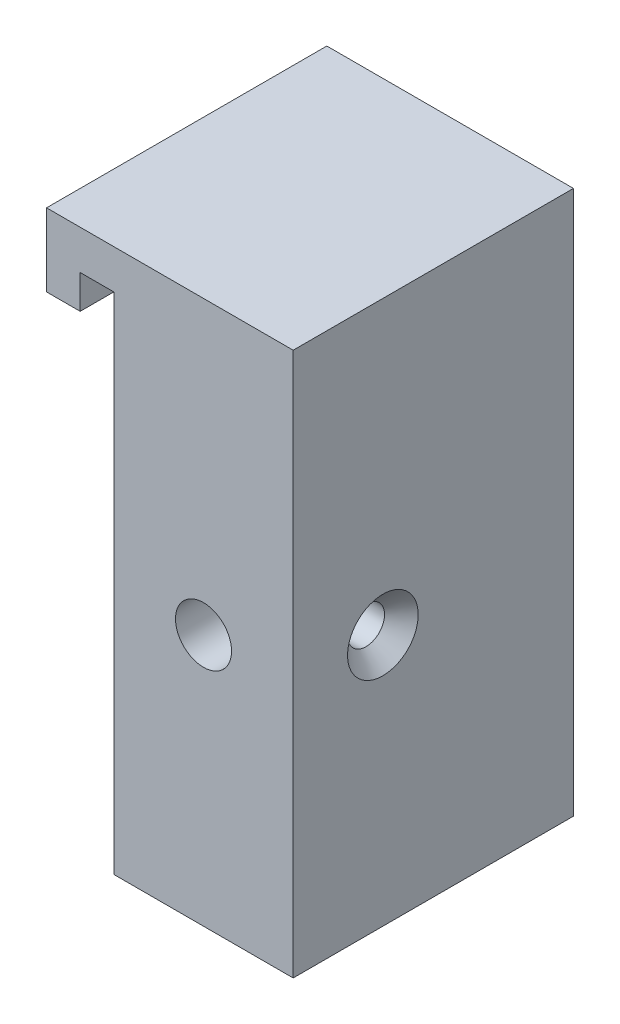
SolidWorks part; units mm, degrees
ref_plane "Front Plane" through (0, 0, 0) normal (0, 0, 1) x (1, 0, 0)
ref_plane "Top Plane" through (0, 0, 0) normal (0, 1, 0) x (1, 0, 0)
ref_plane "Right Plane" through (0, 0, 0) normal (1, 0, 0) x (0, 0, -1)
sketch "Sketch1" plane through (0, 0, 0) normal (0, 0, 1) x (1, 0, 0)
  line L0 (0, 0) -> (0, 97)
  line L1 (0, 97) -> (-44, 97)
  line L2 (-44, 97) -> (-44, 84)
  line L3 (-44, 84) -> (-38, 84)
  line L5 (-32, 0) -> (0, 0)
  line L6 (-38, 84) -> (-38, 90)
  line L7 (-38, 90) -> (-32, 90)
  line L8 (-32, 90) -> (-32, 0)
  dimension "D1" = 32
  dimension "D2" = 44
  dimension "D3" = 6
  dimension "D4" = 13
  dimension "D5" = 7
  dimension "D6" = 97
extrude "Boss-Extrude1" add sketch "Sketch1" along normal mid plane 50
hole_wizard "Ø10.0mm Dowel Hole1" positions "Sketch3" profile "Sketch4" hole size "Ø10.0" standard "ISO"
sketch "Sketch3" plane through (0, 0, 25) normal (0, 0, 1) x (1, 0, 0)
  line L0 (-32, 0) -> (0, 0) construction
  line L1 (0, 0) -> (0, 97) construction
  point P0 (-16, 45)
  dimension "D1" = 45
  dimension "D2" = 16
sketch "Sketch4" plane through (-16, 45, 25) normal (1, 0, 0) x (0, -1, 0)
  line L0 (0, 0) -> (0, 25)
  line L1 (0, 25) -> (5, 25)
  line L2 (5, 25) -> (5, 0)
  line L5 (5, 0) -> (0, 0)
  line L10 (0, 25) -> (-5, 25) construction
  line L11 (0, -6.35) -> (0, 107.95) construction
  dimension "Hole Dia." = 10
  dimension "Hole Depth" = 25
  dimension "Drill Angle" = 180
hole_wizard "M8 Tapped Hole1" positions "Sketch5" profile "Sketch6" tap size "M8" standard "ISO"
sketch "Sketch5" plane through (0, 0, 0) normal (0, -1, 0) x (-1, 0, 0)
  line L0 (16, -25) -> (16, 9.3656) construction
  line L1 (32, -25) -> (0, -25) construction
  line L3 (0, -25) -> (0, 25) construction
  point P0 (7, 0)
  point P2 (25, 0)
  point P13 (0, 0)
  dimension "D1" = 18
  dimension "D2" = 7
sketch "Sketch6" plane through (-7, 0, 0) normal (1, 0, 0) x (0, 0, -1)
  line L0 (0, 0) -> (0, 15)
  line L1 (0, 15) -> (3.4, 15)
  line L2 (3.4, 15) -> (3.4, 0)
  line L5 (3.4, 0) -> (0, 0)
  line L10 (0, 15) -> (-3.4, 15) construction
  line L11 (0, -6.35) -> (0, 107.95) construction
  dimension "Tap Drill Dia." = 6.8
  dimension "Tap Drill Depth" = 15
  dimension "Drill Angle" = 180
hole_wizard "CSK for M6 Countersunk Flat Head Screw1" positions "Sketch7" profile "Sketch8" countersink size "M6" standard "ISO" end condition up to next
sketch "Sketch7" plane through (0, 0, 0) normal (1, 0, 0) x (0, 0, -1)
  line L0 (-25, 0) -> (25, 0) construction
  line L1 (-25, 0) -> (-25, 97) construction
  point P0 (-9, 45)
  dimension "D1" = 45
  dimension "D2" = 16
sketch "Sketch8" plane through (0, 45, 9) normal (0, 1, 0) x (0, 0, -1)
  line L0 (0, 0) -> (0, 11)
  line L1 (0, 11) -> (3.3, 11)
  line L2 (3.3, 11) -> (3.3, 3)
  line L3 (3.3, 3) -> (6.3, 0)
  line L5 (6.3, 0) -> (0, 0)
  line L6 (-3.3, 3) -> (-6.3, 0) construction
  line L11 (0, -6.35) -> (0, 107.95) construction
  dimension "Thru Hole Dia." = 6.6
  dimension "Thru Hole Depth" = 11
  dimension "Near C'Sink Dia." = 12.6
  dimension "Near C'Sink Angle" = 90
